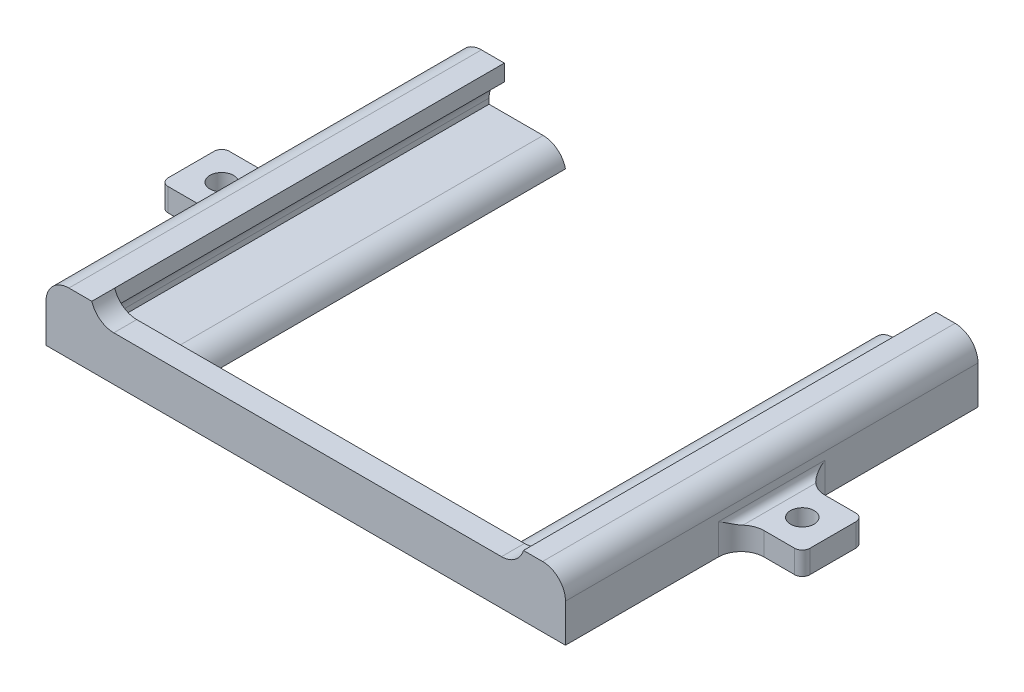
SolidWorks part; units mm, degrees
note: The reader was unsure of these and kept them because the rebuilt part matched: shared geometry of "Sketch2<3>", "Sketch1<3>".
ref_plane "Front Plane" through (0, 0, 0) normal (0, 0, 1) x (1, 0, 0)
ref_plane "Top Plane" through (0, 0, 0) normal (0, 1, 0) x (1, 0, 0)
ref_plane "Right Plane" through (0, 0, 0) normal (1, 0, 0) x (0, 0, -1)
sketch "Sketch1" plane through (0, 0, 0) normal (0, 1, 0) x (1, 0, 0)
  line L0 (0, 0) -> (0, 45.6142) construction
  line L1 (34, 27) -> (-34, 27)
  line L2 (34, 27) -> (34, -27)
  line L3 (34, -27) -> (-34, -27)
  line L4 (-34, 27) -> (-34, -27)
  line L5 (34, 27) -> (-34, -27) construction
  line L6 (34, -27) -> (-34, 27) construction
  line L7 (0, 0) -> (-51.9901, 0) construction
  line L8 (-34, 4) -> (-42, 4)
  line L9 (-34, 4) -> (-34, -4)
  line L10 (-34, -4) -> (-42, -4)
  line L11 (-42, 4) -> (-42, -4)
  line L12 (-38, -4) -> (-38, 20.1825) construction
  line L13 (34, -4) -> (42, -4)
  line L14 (42, 4) -> (42, -4)
  line L15 (34, 4) -> (42, 4)
  circle A0 centre (-38, 0) radius 1.55
  circle A1 centre (38, 0) radius 1.55
  point P0 (0, 0)
  dimension "D6" = 3.1
  dimension "D1" = 68
  dimension "D2" = 54
  dimension "D3" = 8
  dimension "D4" = 8
  dimension "D5" = 4
extrude "Boss-Extrude1" add sketch "Sketch1" along normal blind 8 contours L1 L4 L3 L2
sketch "Sketch2" plane through (0, 0, -27) normal (0, 0, -1) x (-1, 0, 0)
  line L0 (0, 0) -> (0, 24.3026) construction
  line L1 (-30.5, 5.859) -> (30, 5.859)
  line L2 (-30.5, 5.859) -> (-30.5, 2.3342)
  line L3 (-30.5, 2.3342) -> (30, 2.3342)
  line L4 (30, 5.859) -> (30, 2.3342)
  line L5 (-34, 0) -> (34, 0) construction
  line L6 (-34, 8) -> (34, 8) construction
  line L7 (-28.5, 8) -> (28, 8)
  line L8 (-28.5, 8) -> (-28.5, 5.859)
  line L9 (-28.5, 5.859) -> (28, 5.859)
  line L10 (28, 8) -> (28, 5.859)
  line M9 (34, 8) -> (-34, 8)
  dimension "D1" = 60.5
  dimension "D2" = 30
  dimension "D3" = 2
  dimension "D4" = 2
extrude "Cut-Extrude1" cut sketch "Sketch2" against normal blind 51 contours L3 L0 L1 L2 | L0 L3 L4 L1 L9
extrude "Cut-Extrude2" cut sketch "Sketch2<3>" against normal through all contours L1 L0 L7 L8 | L0 L9 L10 M9
sketch "Sketch2<3>" plane through (0, 0, -27) normal (0, 0, -1) x (-1, 0, 0) same geometry as "Sketch2"
fillet "Fillet1" radius 3 2 edges at (30.5, 5.859, -1.5) (-30, 5.859, -1.5)
fillet "Fillet2" radius 3 2 edges at (-34, 8, 0) (34, 8, 0)
sketch "Sketch3" plane through (0, 0, -27) normal (0, 0, -1) x (-1, 0, 0)
  line L0 (-34, 0) -> (34, 0) construction
  line L1 (-20, 0) -> (20, 0)
  line L2 (-20, 0) -> (-20, 2.3342)
  line L3 (-20, 2.3342) -> (20, 2.3342)
  line L4 (20, 0) -> (20, 2.3342)
  line L5 (-30.5, 2.3342) -> (30, 2.3342) construction
  line L6 (0, 0) -> (0, 25.1048) construction
  dimension "D1" = 40
  dimension "D2" = 20
extrude "Cut-Extrude3" cut sketch "Sketch3" against normal blind 51
fillet "Fillet3" radius 3 2 edges at (20, 1.1671, 24) (-20, 1.1671, 24)
fillet "Fillet4" radius 3 4 edges at (-19.1213, 2.3342, 23.1213) (19.1213, 2.3342, 23.1213) (-20, 2.3342, -3) (20, 2.3342, -3)
fillet "Fillet5" radius 3 2 edges at (28.5, 5.859, 25.5) (-28, 5.859, 25.5)
extrude "Boss-Extrude2" add sketch "Sketch1<3>" along normal blind 3 contours L8 L11 L10 L4 A0 | L15 L2 L13 L14 A1
sketch "Sketch1<3>" plane through (0, 0, 0) normal (0, 1, 0) x (1, 0, 0) same geometry as "Sketch1"
fillet "Fillet6" radius 3 4 edges at (34, 1.5, -4) (34, 1.5, 4) (-34, 1.5, -4) (-34, 1.5, 4)
fillet "Fillet7" radius 1 1 edges at (34, 3, 0)
fillet "Fillet8" radius 1 1 edges at (-34, 3, 0)
fillet "Fillet9" radius 1 4 edges at (42, 1.5, -4) (42, 1.5, 4) (-42, 1.5, -4) (-42, 1.5, 4)
